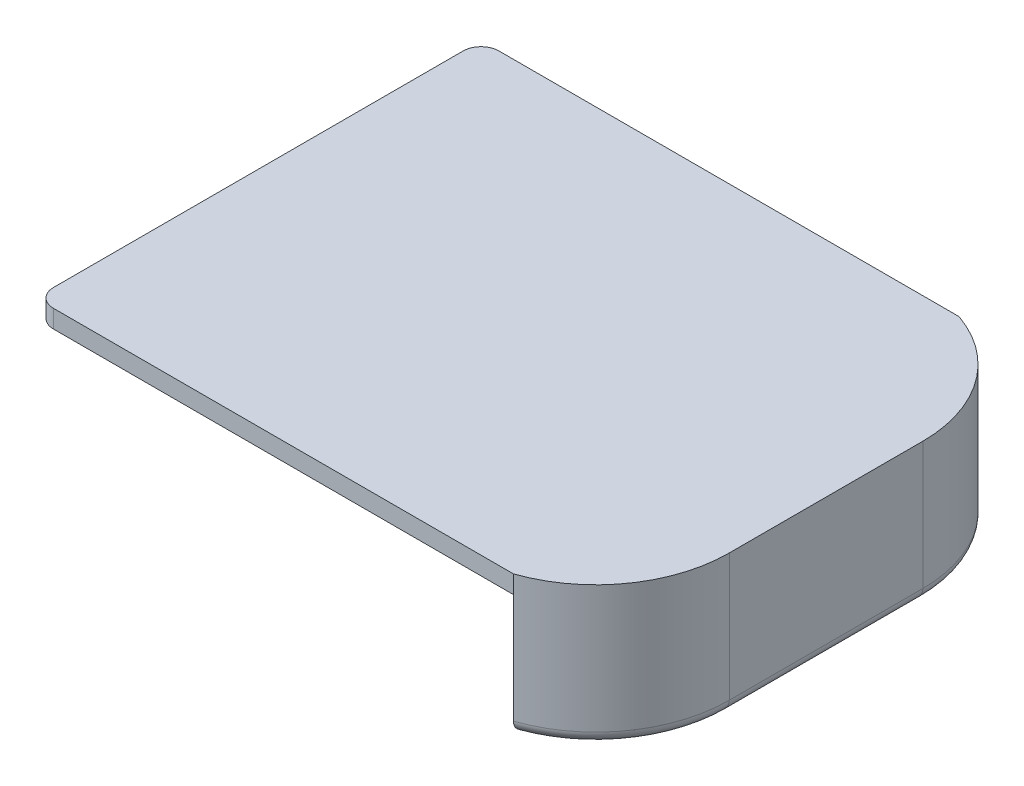
SolidWorks part; units mm, degrees
ref_plane "Front Plane" through (0, 0, 0) normal (0, 0, 1) x (1, 0, 0)
ref_plane "Top Plane" through (0, 0, 0) normal (0, 1, 0) x (1, 0, 0)
ref_plane "Right Plane" through (0, 0, 0) normal (1, 0, 0) x (0, 0, -1)
sketch "Sketch1" plane through (0, 0, 0) normal (0, 1, 0) x (1, 0, 0)
  line L0 (1.0057, -6.715) -> (1.0057, 13.085)
  line L1 (1.0057, 13.085) -> (75.8057, 13.085)
  line L2 (1.0057, -6.715) -> (10.7057, -6.715)
  line L3 (10.7057, -6.715) -> (10.7057, 7.685)
  line L4 (10.7057, -13.515) -> (10.7057, 7.685)
  line L5 (30.7855, -6.715) -> (75.8057, -6.715)
  line L6 (75.8057, -6.715) -> (75.8057, 13.085)
  arc A0 (30.7855, -6.715) -> (10.7057, 7.685) centre (10.7057, -13.515) ccw
  arc A1 (10.7057, 7.685) -> (33.7057, -6.715) centre (10.7057, -17.8831) cw
  arc A2 (10.7057, 7.685) -> (33.7057, -6.715) centre (13.0157, -14.1934) cw
  dimension "D2" = 21.2
  dimension "D1" = 9.7
  dimension "D3" = 19.8
  dimension "D4" = 74.8
  dimension "D5" = 14.4
  dimension "D6" = 19.8
  dimension "D7" = 23
extrude "Boss-Extrude1" add sketch "Sketch1" along normal blind 15.3 contours A0 L5 L6 L1 L0 L2 L3 region at (42.1777, 0, -3.9497)
sketch "Sketch4" plane through (75.8057, 0, 0) normal (1, 0, 0) x (0, 0, -1)
  line L0 (-6.715, 4.35) -> (0.285, 4.35)
  line L1 (-6.715, 15.3) -> (-6.715, 0) construction
  line L2 (0.285, 4.35) -> (0.285, 10.25)
  line L3 (0.285, 10.25) -> (-6.715, 10.25)
  line L4 (-6.715, 10.25) -> (-6.715, 4.35)
  line L5 (-6.715, 0) -> (13.085, 0) construction
  dimension "D1" = 7
  dimension "D2" = 5.9
  dimension "D3" = 4.35
extrude "Cut-Extrude1" cut sketch "Sketch4" against normal through all
sketch "Sketch5" plane through (0, 15.3, 0) normal (0, 1, 0) x (1, 0, 0)
  line L1 (1.0057, 13.085) -> (75.8057, 13.085)
  line L2 (1.0057, 13.085) -> (1.0057, -6.715)
  line L3 (1.0057, -6.715) -> (75.8057, -6.715)
  line L4 (75.8057, 13.085) -> (75.8057, -6.715)
extrude "Boss-Extrude2" add sketch "Sketch5" along normal blind 2
sketch "Sketch6" plane through (0, 0, -13.085) normal (0, 0, -1) x (-1, 0, 0)
  line L0 (-75.8057, 17.3) -> (-75.8057, 20.3)
  line L1 (-1.0057, 17.3) -> (-1.0057, 20.3)
  line L2 (-1.0057, 20.3) -> (-75.8057, 20.3)
  line L3 (-75.8057, 17.3) -> (-1.0057, 17.3)
  dimension "D1" = 3
extrude "Boss-Extrude3" add sketch "Sketch6" against normal blind 37.2
sketch "Sketch7" plane through (1.0057, 0, 0) normal (-1, 0, 0) x (0, 0, 1)
  line L1 (24.115, 17.3) -> (-13.085, 17.3)
  line L2 (24.115, 17.3) -> (24.115, 20.3)
  line L3 (24.115, 20.3) -> (-13.085, 20.3)
  line L4 (-13.085, 17.3) -> (-13.085, 20.3)
extrude "Boss-Extrude4" add sketch "Sketch7" along normal blind 5
fillet "Fillet1" radius 3 1 edges at (-3.9943, 18.8, 24.115)
sketch "Sketch8" plane through (0, 20.3, 0) normal (0, 1, 0) x (1, 0, 0)
  line L0 (75.8057, 13.085) -> (90.8057, 13.085)
  line L1 (90.8057, 13.085) -> (90.8057, -3.0727)
  line L2 (75.8057, 13.085) -> (75.8057, -24.115)
  arc A0 (90.8057, -3.0727) -> (75.8057, -24.115) centre (68.5463, -3.0727) cw
  dimension "D1" = 15
  dimension "D2" = 16.1576
extrude "Boss-Extrude5" add sketch "Sketch8" against normal blind 23.3
fillet "Fillet2" radius 2 2 edges at (90.8057, -3, -5.0062) (86.6718, -3, 15.9934)
sketch "Sketch10" plane through (0, 0, 0) normal (0, -1, 0) x (-1, 0, 0)
  line L1 (-1.0057, -6.715) -> (-75.8057, -6.715)
  line L2 (-1.0057, -6.715) -> (-1.0057, 13.085)
  line L3 (-1.0057, 13.085) -> (-75.8057, 13.085)
  line L4 (-75.8057, -6.715) -> (-75.8057, 13.085)
extrude "Cut-Extrude2" cut sketch "Sketch10" against normal blind 0.2
sketch "Sketch11" plane through (0, -3, 0) normal (0, -1, 0) x (-1, 0, 0)
  line L0 (-75.8057, 13.085) -> (-75.8057, 3.085)
  line L1 (-75.8057, 13.085) -> (-75.8057, -21.9868) construction
  line L2 (-75.8057, 13.085) -> (-83.3057, 13.085)
  line L3 (-88.8057, 13.085) -> (-75.8057, 13.085) construction
  line L4 (-83.3057, 13.085) -> (-83.3057, 8.085)
  arc A1 (-75.8057, 3.085) -> (-83.3057, 8.085) centre (-75.8057, 11.21) cw
  dimension "D1" = 10
  dimension "D2" = 7.5
  dimension "D3" = 5
extrude "Cut-Extrude3" cut sketch "Sketch11" against normal blind 5 draft 30 draft outward yes
sketch "Sketch14" plane through (0, 0, -13.085) normal (0, 0, -1) x (-1, 0, 0)
  line L0 (-72.9189, 2) -> (-73.9582, 0.2)
  line L1 (-73.9582, 0.2) -> (-75.8057, 0.2)
  line L2 (-75.8057, 0.2) -> (-75.8057, 2)
  line L3 (-86.1924, 2) -> (-72.9189, 2) construction
  line L4 (-75.8057, 2) -> (-72.9189, 2)
extrude "Boss-Extrude6" add sketch "Sketch14" against normal blind 15
mirror "Mirror1" about plane through (0, 15.3, -13.085) normal (0, 0, -1) of bodies 111
